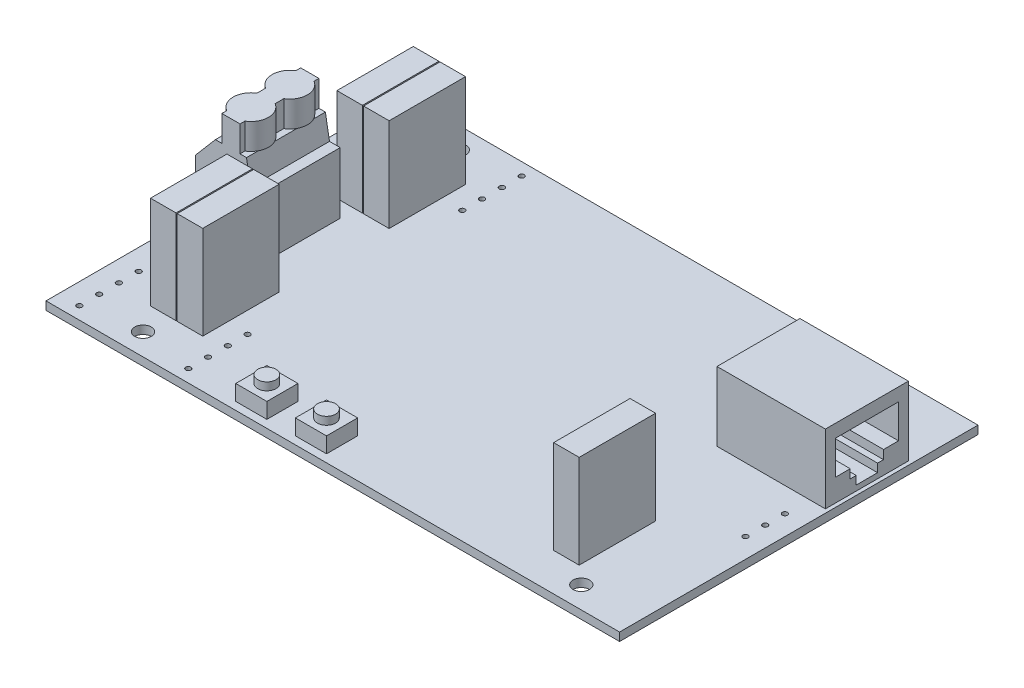
SolidWorks part; units mm, degrees
ref_plane "Front Plane" through (0, 0, 0) normal (0, 0, 1) x (1, 0, 0)
ref_plane "Top Plane" through (0, 0, 0) normal (0, 1, 0) x (1, 0, 0)
ref_plane "Right Plane" through (0, 0, 0) normal (1, 0, 0) x (0, 0, -1)
sketch "Sketch1" plane through (0, 0, 0) normal (0, 1, 0) x (1, 0, 0)
  line L0 (1.4606, 0) -> (0, 0) construction
  line L1 (-55.2894, -34.55) -> (55.2895, -34.55)
  line L2 (-55.2894, -34.55) -> (-55.2894, 34.55)
  line L3 (-55.2894, 34.55) -> (55.2895, 34.55)
  line L4 (55.2895, -34.55) -> (55.2895, 34.55)
  line L5 (-55.2894, -34.55) -> (55.2895, 34.55) construction
  line L6 (-55.2894, 34.55) -> (55.2895, -34.55) construction
  line L7 (-40.7894, -30.35) -> (43.7106, -30.35) construction
  line L8 (-40.7894, -30.35) -> (-40.7894, 30.35) construction
  line L9 (-40.7894, 30.35) -> (43.7106, 30.35) construction
  line L10 (43.7106, -30.35) -> (43.7106, 30.35) construction
  line L11 (-40.7894, -30.35) -> (43.7106, 30.35) construction
  line L12 (-40.7894, 30.35) -> (43.7106, -30.35) construction
  circle A0 centre (-40.7894, -30.35) radius 1.5875
  circle A1 centre (-40.7894, 30.35) radius 1.5875
  circle A2 centre (43.7106, 30.35) radius 1.5875
  circle A3 centre (43.7106, -30.35) radius 1.5875
  point P0 (0, 0)
  point P14 (0, 0)
  dimension "D3" = 3.175
  dimension "D6" = 4.2
  dimension "D7" = 14.5
  dimension "D1" = 69.1
  dimension "D2" = 110.5789
  dimension "D4" = 84.5
  dimension "D5" = 60.7
extrude "Boss-Extrude1" add sketch "Sketch1" against normal blind 1.5875
sketch "Sketch2" plane through (0, 0, 0) normal (0, 1, 0) x (1, 0, 0)
  line L0 (-30.2705, -20.705) -> (-30.2704, -24.515) construction
  line L1 (-30.2704, -24.515) -> (-30.2704, -28.325) construction
  line L2 (-30.2704, -28.325) -> (-30.2704, -32.135) construction
  line L3 (51.4795, 1.137) -> (51.4795, -6.483) construction
  line L4 (51.4795, 1.137) -> (51.4795, -2.673) construction
  line L5 (-30.2705, 24.505) -> (-30.2705, 20.695) construction
  line L6 (-30.2705, 32.125) -> (-30.2705, 28.315) construction
  line L7 (-30.2705, 28.315) -> (-30.2705, 24.505) construction
  line L8 (-51.2705, 28.315) -> (-51.2705, 24.505) construction
  line L9 (-51.2704, -24.515) -> (-51.2704, -28.325) construction
  line L10 (-51.2705, 24.505) -> (-51.2705, 20.695) construction
  line L11 (-51.2704, -28.325) -> (-51.2704, -32.135) construction
  line L12 (-51.2705, 32.125) -> (-51.2705, 28.315) construction
  line L13 (-51.2704, -20.705) -> (-51.2704, -24.515) construction
  line L15 (-55.2894, -34.55) -> (55.2895, -34.55) construction
  line L16 (-55.2894, 34.55) -> (-55.2894, -34.55) construction
  line L17 (55.2895, 34.55) -> (-55.2894, 34.55) construction
  line L18 (55.2895, -34.55) -> (55.2895, 34.55) construction
  circle A0 centre (51.4795, 1.137) radius 0.5
  circle A1 centre (51.4795, -2.673) radius 0.5
  circle A2 centre (51.4795, -6.483) radius 0.5
  circle A3 centre (-30.2705, -20.705) radius 0.5
  circle A4 centre (-30.2704, -24.515) radius 0.5
  circle A5 centre (-30.2704, -28.325) radius 0.5
  circle A6 centre (-30.2704, -32.135) radius 0.5
  circle A7 centre (-30.2705, 32.125) radius 0.5
  circle A8 centre (-30.2705, 20.695) radius 0.5
  circle A9 centre (-30.2705, 24.505) radius 0.5
  circle A10 centre (-30.2705, 28.315) radius 0.5
  circle A11 centre (-51.2705, 28.315) radius 0.5
  circle A12 centre (-51.2705, 24.505) radius 0.5
  circle A13 centre (-51.2704, -28.325) radius 0.5
  circle A14 centre (-51.2704, -20.705) radius 0.5
  circle A15 centre (-51.2704, -24.515) radius 0.5
  circle A16 centre (-51.2705, 32.125) radius 0.5
  circle A17 centre (-51.2704, -32.135) radius 0.5
  circle A18 centre (-51.2705, 20.695) radius 0.5
  dimension "D1" = 25.019
  dimension "D2" = 13.845
  dimension "D3" = 1
  dimension "D4" = 21
  dimension "D5" = 3.81
  dimension "D6" = 66.675
  dimension "D7" = 13.855
  dimension "D8" = 35.687
  dimension "D9" = 3.81
extrude "Cut-Extrude1" cut sketch "Sketch2" against normal through all
sketch "Sketch3" plane through (0, 0, 0) normal (0, 1, 0) x (1, 0, 0)
  line L0 (-34.2894, 10.598) -> (-34.2894, -10.598) construction
  line L1 (-44.3594, -10.598) -> (-39.4395, -10.598)
  line L2 (-44.3594, -10.598) -> (-44.3594, -25.33)
  line L3 (-44.3594, -25.33) -> (-39.4395, -25.33)
  line L4 (-39.4395, -10.598) -> (-39.4395, -25.33)
  line L5 (-44.3594, -10.598) -> (-39.4395, -25.33) construction
  line L6 (-44.3594, -25.33) -> (-39.4395, -10.598) construction
  line L11 (-39.2094, -25.33) -> (-34.2894, -25.33)
  line L12 (-39.2094, -25.33) -> (-39.2094, -10.598)
  line L13 (-39.2094, -10.598) -> (-34.2894, -10.598)
  line L14 (-34.2894, -25.33) -> (-34.2894, -10.598)
  line L15 (-39.2094, -25.33) -> (-34.2894, -10.598) construction
  line L16 (-39.2094, -10.598) -> (-34.2894, -25.33) construction
  line L17 (-39.2094, 10.598) -> (-34.2894, 10.598)
  line L18 (-39.2094, 10.598) -> (-39.2094, 25.33)
  line L19 (-39.2094, 25.33) -> (-34.2894, 25.33)
  line L20 (-34.2894, 10.598) -> (-34.2894, 25.33)
  line L21 (-39.2094, 10.598) -> (-34.2894, 25.33) construction
  line L22 (-39.2094, 25.33) -> (-34.2894, 10.598) construction
  line L23 (-44.3594, 10.598) -> (-39.4395, 10.598)
  line L24 (-44.3594, 10.598) -> (-44.3594, 25.33)
  line L25 (-44.3594, 25.33) -> (-39.4395, 25.33)
  line L26 (-39.4395, 10.598) -> (-39.4395, 25.33)
  line L27 (-44.3594, 10.598) -> (-39.4395, 25.33) construction
  line L28 (-44.3594, 25.33) -> (-39.4395, 10.598) construction
  line L29 (-34.2894, 0) -> (0, 0) construction
  line L30 (-55.2894, 34.55) -> (-55.2894, -34.55) construction
  line L31 (55.2895, -34.55) -> (55.2895, 34.55) construction
  line L32 (35.3095, -12.548) -> (40.2295, -12.548)
  line L33 (35.3095, -12.548) -> (35.3095, -27.28)
  line L34 (35.3095, -27.28) -> (40.2295, -27.28)
  line L35 (40.2295, -12.548) -> (40.2295, -27.28)
  line L36 (35.3095, -12.548) -> (40.2295, -27.28) construction
  line L37 (35.3095, -27.28) -> (40.2295, -12.548) construction
  line L38 (-55.2894, -34.55) -> (55.2895, -34.55) construction
  point P0 (-41.8994, -17.964)
  point P5 (-36.7494, -17.964)
  point P10 (-36.7494, 17.964)
  point P15 (-41.8994, 17.964)
  point P28 (37.7695, -19.914)
  dimension "D1" = 14.732
  dimension "D2" = 10.07
  dimension "D3" = 50.66
  dimension "D4" = 4.92
  dimension "D5" = 10.93
  dimension "D6" = 15.06
  dimension "D7" = 7.27
extrude "Boss-Extrude2" add sketch "Sketch3" along normal blind 18
sketch "Sketch4" plane through (0, 0, 0) normal (0, 1, 0) x (1, 0, 0)
  line L0 (-47.0694, 0) -> (0, 0) construction
  line L1 (-53.4194, -7.605) -> (-40.7194, -7.605)
  line L2 (-53.4194, -7.605) -> (-53.4194, 7.605)
  line L3 (-53.4194, 7.605) -> (-40.7194, 7.605)
  line L4 (-40.7194, -7.605) -> (-40.7194, 7.605)
  line L5 (-53.4194, -7.605) -> (-40.7194, 7.605) construction
  line L6 (-53.4194, 7.605) -> (-40.7194, -7.605) construction
  line L7 (-55.2894, 34.55) -> (-55.2894, -34.55) construction
  point P0 (-47.0694, 0)
  dimension "D1" = 15.21
  dimension "D2" = 12.7
  dimension "D3" = 1.87
extrude "Boss-Extrude3" add sketch "Sketch4" along normal blind 11.8
sketch "Sketch5" plane through (0, 0, 7.605) normal (0, 0, 1) x (1, 0, 0)
  line L0 (-53.4194, 11.8) -> (-40.7194, 11.8) construction
  line L1 (-53.4194, 11.8) -> (-42.7894, 11.8)
  line L2 (-53.4194, 11.8) -> (-49.5829, 16.3)
  line L3 (-49.5829, 16.3) -> (-43.5829, 16.3)
  line L4 (-43.5829, 16.3) -> (-42.7894, 11.8)
  line L5 (-53.4194, 0) -> (-40.7194, 0) construction
  line L6 (-40.7194, 11.8) -> (-40.7194, 0) construction
  dimension "D1" = 16.3
  dimension "D2" = 2.07
  dimension "D3" = 100
  dimension "D4" = 6
extrude "Boss-Extrude4" add sketch "Sketch5" against normal up to surface (15.21 mm away) up to face at (-47.0694, 5.9, -7.605)
sketch "Sketch6" plane through (0, 16.3, 0) normal (0, 1, 0) x (1, 0, 0)
  line L0 (-49.5829, 7.605) -> (-43.5829, 7.605) construction
  line L1 (-48.3329, 7.605) -> (-44.8329, 7.605)
  line L2 (-48.3329, 7.605) -> (-48.3329, 6.665)
  line L3 (-48.3329, -7.605) -> (-44.8329, -7.605)
  line L4 (-44.8329, 7.605) -> (-44.8329, 6.665)
  line L5 (-43.5829, -7.605) -> (-49.5829, -7.605) construction
  line L6 (-46.5829, 3.75) -> (-46.5829, -3.75) construction
  line L7 (-44.8329, 0) -> (-48.3329, 0) construction
  line L8 (-48.3329, -6.665) -> (-48.3329, -7.605)
  line L9 (-48.3329, 0.835) -> (-48.3329, -0.835)
  line L10 (-44.8329, 0.835) -> (-44.8329, -0.835)
  line L11 (-44.8329, -6.665) -> (-44.8329, -7.605)
  arc A0 (-48.3329, -0.835) -> (-48.3329, -6.665) centre (-46.5829, -3.75) ccw
  arc A1 (-44.8329, 0.835) -> (-44.8329, 6.665) centre (-46.5829, 3.75) ccw
  arc A2 (-48.3329, 6.665) -> (-48.3329, 0.835) centre (-46.5829, 3.75) ccw
  arc A3 (-44.8329, -6.665) -> (-44.8329, -0.835) centre (-46.5829, -3.75) ccw
  point P8 (-46.5829, -7.605)
  point P15 (-46.5829, 0)
  dimension "D2" = 6.8
  dimension "D3" = 7.5
  dimension "D1" = 3.5
extrude "Boss-Extrude5" add sketch "Sketch6" along normal blind 5
sketch "Sketch7" plane through (0, 0, 0) normal (0, 1, 0) x (1, 0, 0)
  line L0 (55.2895, 34.55) -> (-55.2894, 34.55) construction
  line L1 (33.6695, 5.85) -> (54.5695, 5.85)
  line L2 (33.6695, 5.85) -> (33.6695, 21.85)
  line L3 (33.6695, 21.85) -> (54.5695, 21.85)
  line L4 (54.5695, 5.85) -> (54.5695, 21.85)
  line L5 (55.2895, -34.55) -> (55.2895, 34.55) construction
  dimension "D1" = 12.7
  dimension "D2" = 0.72
  dimension "D3" = 16
  dimension "D4" = 20.9
extrude "Boss-Extrude6" add sketch "Sketch7" along normal blind 13.33
sketch "Sketch8" plane through (54.5695, 0, 0) normal (1, 0, 0) x (0, 0, -1)
  line L0 (15.91, 2.6125) -> (17.06, 2.6125)
  line L1 (7.75, 10.83) -> (19.95, 10.83)
  line L2 (7.75, 10.83) -> (7.75, 4.3125)
  line L3 (7.75, 4.3125) -> (10.64, 4.3125)
  line L4 (19.95, 10.83) -> (19.95, 4.3125)
  line L6 (10.64, 4.3125) -> (10.64, 2.6125)
  line L7 (10.64, 2.6125) -> (11.79, 2.6125)
  line L8 (17.06, 4.3125) -> (17.06, 2.6125)
  line L10 (11.79, 2.6125) -> (11.79, 1.0125)
  line L11 (11.79, 1.0125) -> (15.91, 1.0125)
  line L12 (15.91, 2.6125) -> (15.91, 1.0125)
  line L13 (17.06, 4.3125) -> (19.95, 4.3125)
  line L14 (13.85, 10.83) -> (13.85, 13.33) construction
  line L15 (5.85, 13.33) -> (21.85, 13.33) construction
  line L16 (5.85, 13.33) -> (5.85, 0) construction
  line L17 (-34.55, -1.5875) -> (34.55, -1.5875) construction
  dimension "D1" = 1.9
  dimension "D2" = 2.5
  dimension "D3" = 2.6
  dimension "D4" = 4.2
  dimension "D5" = 5.9
  dimension "D6" = 6.42
  dimension "D7" = 4.12
extrude "Cut-Extrude2" cut sketch "Sketch8" against normal blind 10.5
sketch "Sketch9" plane through (0, 0, 0) normal (0, 1, 0) x (1, 0, 0)
  line L0 (-55.2894, -34.55) -> (55.2895, -34.55) construction
  line L1 (-20.2105, -27.05) -> (-14.2105, -27.05)
  line L2 (-20.2105, -27.05) -> (-20.2105, -33.05)
  line L3 (-20.2105, -33.05) -> (-14.2105, -33.05)
  line L4 (-14.2105, -27.05) -> (-14.2105, -33.05)
  line L5 (-8.7105, -27.05) -> (-2.7105, -27.05)
  line L6 (-8.7105, -27.05) -> (-8.7105, -33.05)
  line L7 (-8.7105, -33.05) -> (-2.7105, -33.05)
  line L8 (-2.7105, -27.05) -> (-2.7105, -33.05)
  line L9 (55.2895, -34.55) -> (55.2895, 34.55) construction
  dimension "D1" = 6
  dimension "D2" = 1.5
  dimension "D3" = 17.5
  dimension "D4" = 58
extrude "Boss-Extrude7" add sketch "Sketch9" along normal blind 3
sketch "Sketch10" plane through (0, 3, 0) normal (0, 1, 0) x (1, 0, 0)
  line L0 (-14.2105, -27.05) -> (-20.2105, -33.05) construction
  line L1 (-2.7105, -27.05) -> (-8.7105, -33.05) construction
  circle A0 centre (-17.2105, -30.05) radius 1.75
  circle A1 centre (-5.7105, -30.05) radius 1.75
  dimension "D1" = 3.5
extrude "Boss-Extrude8" add sketch "Sketch10" along normal blind 1.5
